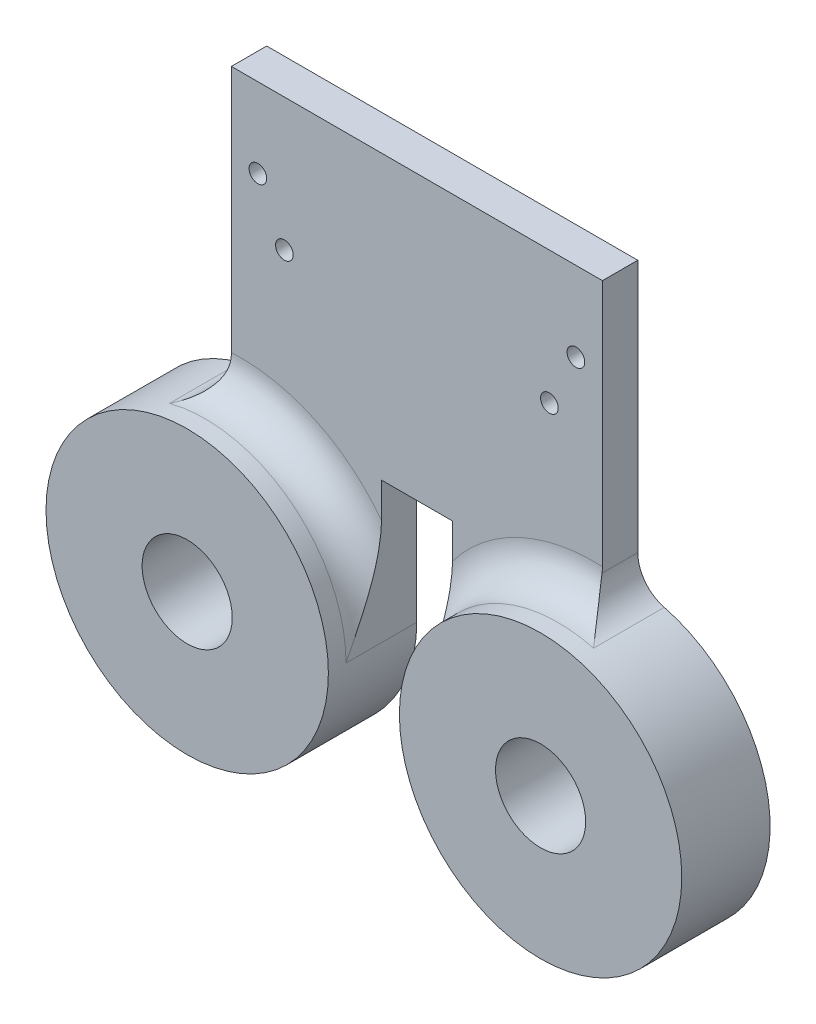
SolidWorks part; units mm, degrees
ref_plane "Front Plane" through (0, 0, 0) normal (0, 0, 1) x (1, 0, 0)
ref_plane "Top Plane" through (0, 0, 0) normal (0, 1, 0) x (1, 0, 0)
ref_plane "Right Plane" through (0, 0, 0) normal (1, 0, 0) x (0, 0, -1)
sketch "Sketch1" plane through (0, 0, 0) normal (0, 0, 1) x (1, 0, 0)
  line L0 (-10, -12.5) -> (-10, -15.5) construction
  line L2 (-10.5, -7.5251) -> (-10.5, 8.5)
  line L3 (-10.5, 8.5) -> (10.5, 8.5)
  line L4 (10.5, -7.5251) -> (10.5, 8.5)
  line L5 (-10.5, -8.5) -> (10.5, 8.5) construction
  line L6 (-10.5, 8.5) -> (10.5, -8.5) construction
  line L10 (0, -12.5) -> (0, -10.7832) construction
  line L12 (-10, -12.5) -> (10, -12.5) construction
  line L13 (-2.0094, -15.5) -> (-2.0094, -7.5251)
  line L14 (2.0094, -15.5) -> (2.0094, -7.5251)
  line L15 (-2.0094, -7.5251) -> (2.0094, -7.5251)
  circle A5 centre (-10, -15.5) radius 2.55
  circle A7 centre (10, -15.5) radius 2.55
  arc A8 (10.5, -7.5251) -> (2.0094, -15.5) centre (10, -15.5) cw
  arc A9 (-10.5, -7.5251) -> (-2.0094, -15.5) centre (-10, -15.5) ccw
  point P0 (0, 0)
extrude "Boss-Extrude1" add sketch "Sketch1" along normal blind 2
sketch "Sketch2" plane through (0, 0, 0) normal (0, 0, 1) x (1, 0, 0)
  circle A4 centre (-10, -15.5) radius 2.55
  circle A5 centre (-10, -15.5) radius 7.9906
  circle A6 centre (10, -15.5) radius 2.55
  circle A7 centre (10, -15.5) radius 7.9906
extrude "Boss-Extrude2" add sketch "Sketch2" along normal blind 5
fillet "Fillet1" radius 2 4 edges at (-4.5294, -9.6757, 2) (-10.5, -7.5251, 1) (4.5294, -9.6757, 2) (10.5, -7.5251, 1)
sketch "Sketch3" plane through (0, 0, 0) normal (0, 0, 1) x (1, 0, 0)
  line L0 (0, 8.5) -> (0, 4) construction
  line L1 (10.5, 8.5) -> (-10.5, 8.5) construction
  line L2 (10.5, 4) -> (9, 4) construction
  line L3 (10.5, -5.5219) -> (10.5, 8.5) construction
  line L4 (0, 4) -> (0, 1) construction
  line L5 (-10.5, 1) -> (-7.5, 1) construction
  line L6 (-10.5, 8.5) -> (-10.5, -5.5219) construction
  circle A0 centre (9, 4) radius 0.5
  circle A1 centre (-9, 4) radius 0.5
  circle A2 centre (-7.5, 1) radius 0.5
  circle A3 centre (7.5, 1) radius 0.5
extrude "Cut-Extrude1" cut sketch "Sketch3" along normal blind 5
